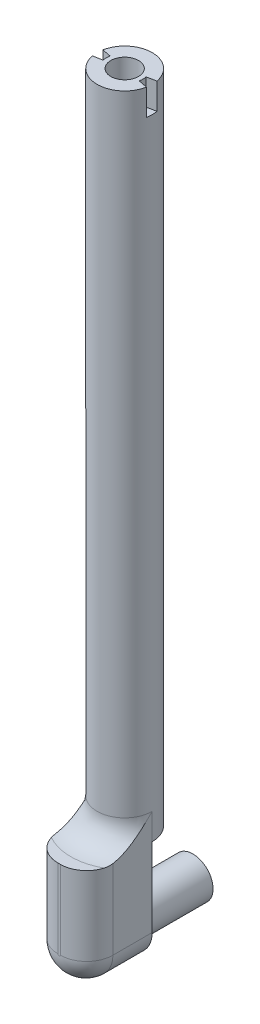
SolidWorks part; units mm, degrees
ref_plane "Front Plane" through (0, 0, 0) normal (0, 0, 1) x (1, 0, 0)
ref_plane "Top Plane" through (0, 0, 0) normal (0, 1, 0) x (1, 0, 0)
ref_plane "Right Plane" through (0, 0, 0) normal (1, 0, 0) x (0, 0, -1)
sketch "Sketch3" plane through (0, 0, 0) normal (0, 1, 0) x (1, 0, 0)
  circle A0 centre (0, 0) radius 5.25
  dimension "D1" = 10.5
extrude "Boss-Extrude1" add sketch "Sketch3" along normal blind 120
sketch "Sketch4" plane through (0, 0, 0) normal (0, 0, 1) x (1, 0, 0)
  line L1 (-5.25, 0) -> (-5.25, -15)
  line L2 (-5.25, 0) -> (5.25, 0) construction
  line L3 (5.25, -15) -> (5.25, 0)
  line L4 (-5.25, 0) -> (5.25, 0)
  arc A1 (-5.25, -15) -> (5.25, -15) centre (0, -15) ccw
  dimension "D1" = 15
extrude "Boss-Extrude4" add sketch "Sketch4" along normal blind 12.5
sketch "Sketch6" plane through (0, 0, 0) normal (0, 0, -1) x (-1, 0, 0)
  line L0 (-5.25, 0) -> (5.25, 0) construction
  circle A0 centre (0, -15) radius 3.85
  dimension "D1" = 7.7
  dimension "D2" = 15
extrude "Boss-Extrude5" add sketch "Sketch6" along normal blind 13
fillet "Fillet3" radius 5 1 edges at (0, 0, 5.25)
fillet "Fillet4" radius 5 3 edges at (5.25, -7.5, 12.5) (0, -20.25, 12.5) (-5.25, -7.5, 12.5)
sketch "Sketch7" plane through (0, 120, 0) normal (0, 1, 0) x (1, 0, 0)
  circle A0 centre (0, 0) radius 2.65
  dimension "D1" = 5.3
extrude "Cut-Extrude1" cut sketch "Sketch7" against normal blind 8
sketch "Sketch9" plane through (0, 120, 0) normal (0, 1, 0) x (1, 0, 0)
  line L0 (0, 0) -> (2.6015, 0.5048) construction
  line L1 (0, 0) -> (2.6015, -0.5048) construction
  line L2 (0, 0) -> (-2.6015, 0.5048) construction
  line L3 (0, 0) -> (-2.6015, -0.5048) construction
  line L8 (-3.4359, 0.6667) -> (-5.1539, 1)
  line L9 (-3.4359, -0.6667) -> (-5.1539, -1)
  line L10 (3.4359, -0.6667) -> (5.1539, -1)
  line L11 (3.4359, 0.6667) -> (5.1539, 1)
  line L12 (-3.4359, 0.6667) -> (-5.1539, 1) construction
  line L13 (-3.4359, -0.6667) -> (-5.1539, -1) construction
  line L14 (3.4359, -0.6667) -> (5.1539, -1) construction
  line L15 (3.4359, 0.6667) -> (5.1539, 1) construction
  arc A0 (-5.1539, 1) -> (-5.1539, -1) centre (0, 0) ccw construction
  arc A1 (-3.4359, 0.6667) -> (-3.4359, -0.6667) centre (0, 0) ccw
  arc A2 (5.1539, -1) -> (5.1539, 1) centre (0, 0) ccw construction
  arc A3 (3.4359, -0.6667) -> (3.4359, 0.6667) centre (0, 0) ccw
  arc A4 (-5.1539, 1) -> (5.1539, 1) centre (0, 0) cw
  arc A5 (-5.1539, -1) -> (5.1539, -1) centre (0, 0) ccw
  arc A6 (-2.6015, 0.5048) -> (2.6015, 0.5048) centre (0, 0) cw
  circle A7 centre (0, 0) radius 5.25 construction
  arc A8 (-2.6015, 0.5048) -> (-2.6015, -0.5048) centre (0, 0) ccw
  circle A9 centre (0, 0) radius 2.65 construction
  arc A10 (2.6015, -0.5048) -> (2.6015, 0.5048) centre (0, 0) ccw
  arc A11 (-2.6015, -0.5048) -> (2.6015, -0.5048) centre (0, 0) ccw
  dimension "D3" = 3.5
  dimension "D1" = 1
  dimension "D2" = 1
extrude "Boss-Extrude6" add sketch "Sketch9" along normal blind 5
